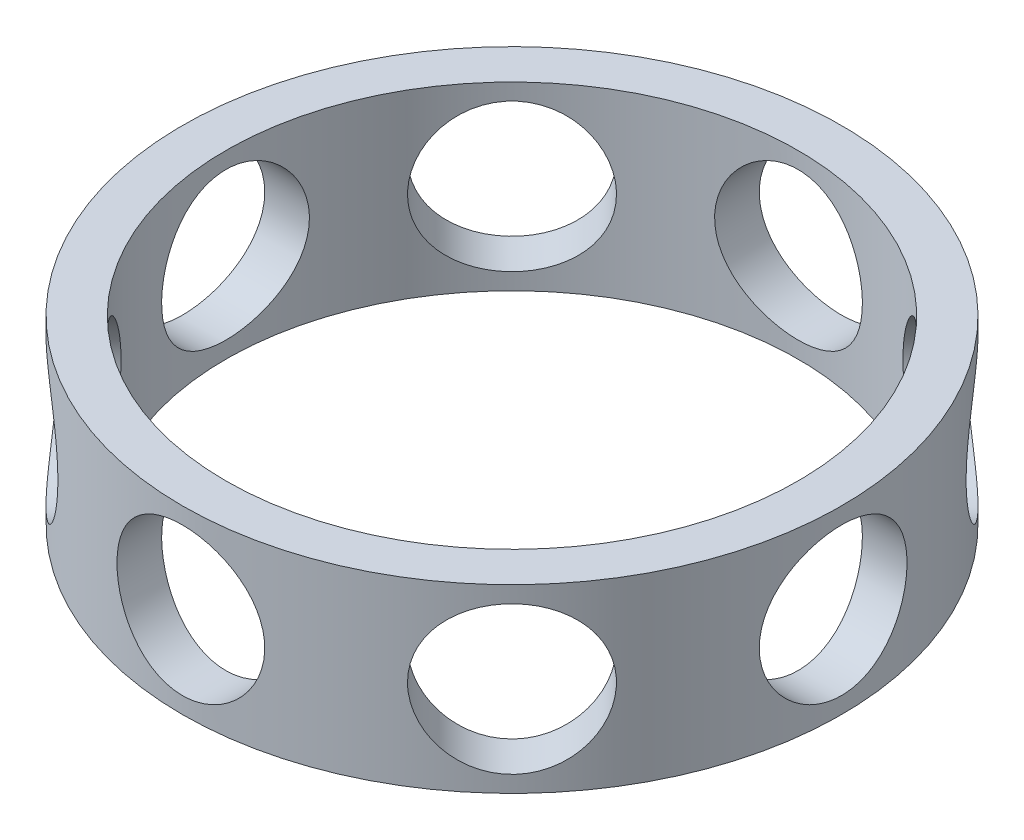
SolidWorks part; units mm, degrees
material "AISI Type 316L stainless steel"
ref_plane "Front Plane" through (0, 0, 0) normal (0, 0, 1) x (1, 0, 0)
ref_plane "Top Plane" through (0, 0, 0) normal (0, 1, 0) x (1, 0, 0)
ref_plane "Right Plane" through (0, 0, 0) normal (1, 0, 0) x (0, 0, -1)
sketch "Sketch1" plane through (0, 0, 0) normal (0, 1, 0) x (1, 0, 0)
  circle A0 centre (0, 0) radius 2.9515
  circle A1 centre (0, 0) radius 3.3985
  dimension "D1" = 5.903
  dimension "D2" = 6.797
extrude "Boss-Extrude1" add sketch "Sketch1" along normal blind 0.9322 and the other way blind 0.9322
sketch "Sketch3" plane through (0, 0, 0) normal (0, 0, 1) x (1, 0, 0)
  circle A0 centre (0, 0) radius 0.762
  dimension "D1" = 1.524
extrude "Cut-Extrude1" cut sketch "Sketch3" against normal up to surface (3.312 mm away) up to face at (0, -0.9322, 3.3985)
ref_axis "Axis1" through (0, 0, 0) along (0, 1, 0)
pattern_circular "CirPattern1" count 8 over 360 about axis through (0, 0, 0) along (0, 1, 0) of "Cut-Extrude1"
